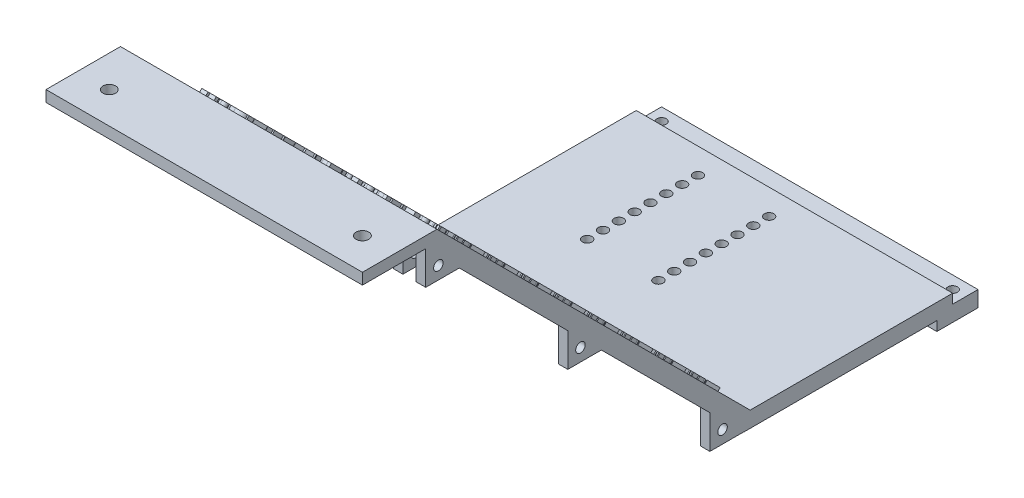
SolidWorks part; units mm, degrees
ref_plane "Front Plane" through (0, 0, 0) normal (0, 0, 1) x (1, 0, 0)
ref_plane "Top Plane" through (0, 0, 0) normal (0, 1, 0) x (1, 0, 0)
ref_plane "Right Plane" through (0, 0, 0) normal (1, 0, 0) x (0, 0, -1)
sketch "Sketch4" plane through (0, 0, 0) normal (1, 0, 0) x (0, 0, -1)
  line L0 (0, 0) -> (-8, 0)
  line L1 (-8, 0) -> (-8, 3)
  line L2 (-8, 3) -> (-72, 3)
  line L3 (-72, 3) -> (-170.9949, 101.9949)
  dimension "D1" = 8
  dimension "D2" = 3
  dimension "D3" = 64
  dimension "D4" = 135
  dimension "D5" = 140
extrude "Extrude-Thin2" add sketch "Sketch4" along normal blind 100 thin thin type one direction reverse wall 5
sketch "Sketch5" plane through (0, 3, 0) normal (0, 1, 0) x (1, 0, 0)
  line L1 (100, -8) -> (100, -72) construction
  line L2 (100, -8) -> (0, -8) construction
  circle A0 centre (50, -16) radius 1.5
  dimension "D2" = 3
  dimension "D1" = 50
  dimension "D3" = 8
extrude "Cut-Extrude1" cut sketch "Sketch5" against normal up to next
pattern_linear "LPattern1" count 8 spacing 5 along (0, 0, 1) count 2 spacing 22.5 along (-1, 0, 0) of "Cut-Extrude1"
sketch "Sketch7" plane through (100, 0, 0) normal (1, 0, 0) x (0, 0, -1)
  line L0 (-170.9949, 101.9949) -> (-174.5305, 101.9949)
  line L1 (-174.5305, 101.9949) -> (-174.5305, 98.4594)
  line L2 (-174.5305, 98.4594) -> (-170.9949, 101.9949)
extrude "Boss-Extrude1" add sketch "Sketch7" against normal up to surface (100 mm away) up to face at (0, 19.2454, 53.3597)
sketch "Sketch8" plane through (0, 0, 174.5305) normal (0, 0, 1) x (1, 0, 0)
  line L1 (0, 101.9949) -> (100, 101.9949)
  line L2 (0, 101.9949) -> (0, 98.4594)
  line L3 (0, 98.4594) -> (100, 98.4594)
  line L4 (100, 101.9949) -> (100, 98.4594)
extrude "Boss-Extrude2" add sketch "Sketch8" along normal blind 20
sketch "Sketch9" plane through (0, 101.9949, 0) normal (0, 1, 0) x (1, 0, 0)
  line L0 (100, -170.9949) -> (100, -194.5305) construction
  line L1 (100, -194.5305) -> (0, -194.5305) construction
  line L2 (0, -170.9949) -> (0, -194.5305) construction
  circle A0 centre (90, -184.5305) radius 2
  circle A1 centre (10, -184.5305) radius 2
  dimension "D1" = 4
  dimension "D2" = 4
  dimension "D3" = 10
  dimension "D4" = 10
  dimension "D5" = 10
  dimension "D6" = 10
extrude "Cut-Extrude2" cut sketch "Sketch9" against normal up to next
sketch "Sketch10" plane through (0, 0, 0) normal (0, 1, 0) x (1, 0, 0)
  line L0 (100, 0) -> (0, 0) construction
  line L1 (100, 0) -> (100, -8) construction
  line L2 (0, 0) -> (0, -8) construction
  circle A0 centre (4, -4) radius 1.5
  circle A1 centre (96, -4) radius 1.5
  dimension "D1" = 3
  dimension "D2" = 3
  dimension "D3" = 4
  dimension "D4" = 4
  dimension "D5" = 4
extrude "Cut-Extrude3" cut sketch "Sketch10" against normal up to next
sketch "Sketch11" plane through (100, 0, 0) normal (1, 0, 0) x (0, 0, -1)
  line L0 (-174.5305, 98.4594) -> (-174.5305, 87.8528)
  line L1 (-174.5305, 87.8528) -> (-163.9239, 87.8528)
  line L2 (-74.0711, -2) -> (-174.5305, 98.4594) construction
  line L3 (-174.5305, 98.4594) -> (-163.9239, 87.8528)
  dimension "D1" = 15
extrude "Boss-Extrude3" add sketch "Sketch11" against normal blind 3
sketch "Sketch12" plane through (100, 0, 0) normal (1, 0, 0) x (0, 0, -1)
  line L0 (-174.5305, 98.4594) -> (-174.5305, 87.8528) construction
  line L1 (-174.5305, 87.8528) -> (-163.9239, 87.8528) construction
  circle A0 centre (-170.5305, 91.8528) radius 1.5
  dimension "D1" = 3
  dimension "D2" = 4
  dimension "D3" = 4
extrude "Cut-Extrude4" cut sketch "Sketch12" against normal up to next
pattern_linear "LPattern2" count 3 spacing 63.5 along (0, -0.7071, -0.7071) count 2 spacing 97 along (-1, 0, 0) of "Boss-Extrude3", "Cut-Extrude4"
sketch "Sketch13" plane through (0, -2, 0) normal (0, -1, 0) x (1, 0, 0)
  line L0 (0, 13) -> (0, 74.0711) construction
  line L1 (0, 48.535) -> (3, 48.535)
  line L2 (0, 48.535) -> (0, 38.535)
  line L3 (0, 38.535) -> (3, 38.535)
  line L4 (3, 48.535) -> (3, 38.535)
  dimension "D1" = 3
  dimension "D2" = 10
  dimension "D3" = 25.535
extrude "Boss-Extrude4" add sketch "Sketch13" along normal blind 10
sketch "Sketch14" plane through (0, 0, 0) normal (-1, 0, 0) x (0, 0, 1)
  line L0 (38.535, -12) -> (38.535, -2) construction
  line L1 (48.535, -12) -> (38.535, -12) construction
  circle A0 centre (43.535, -7) radius 1.5
  dimension "D1" = 3
  dimension "D2" = 5
  dimension "D3" = 5
extrude "Cut-Extrude5" cut sketch "Sketch14" against normal up to next
sketch "Sketch15" plane through (0, -34.5, 34.5) normal (0, 0.7071, -0.7071) x (1, 0, 0)
  line L0 (100, -53.033) -> (100, -193.033) construction
  line L1 (100, -193.033) -> (0, -193.033) construction
  circle A0 centre (84, -176.233) radius 3.4
  circle A1 centre (84, -161.233) radius 3.4
  circle A2 centre (84, -146.233) radius 3.4
  circle A5 centre (84, -131.233) radius 3.4
  circle A6 centre (84, -116.233) radius 3.4
  circle A7 centre (84, -101.233) radius 3.4
  circle A8 centre (84, -86.233) radius 3.4
  circle A9 centre (84, -71.233) radius 3.4
  dimension "D1" = 6.8
  dimension "D2" = 6.8
  dimension "D3" = 6.8
  dimension "D8" = 6.8
  dimension "D9" = 6.8
  dimension "D10" = 6.8
  dimension "D11" = 6.8
  dimension "D16" = 6.8
  dimension "D4" = 16
  dimension "D5" = 16.8
  dimension "D6" = 15
  dimension "D7" = 15
  dimension "D12" = 15
  dimension "D13" = 15
  dimension "D14" = 15
  dimension "D15" = 15
  dimension "D17" = 15
extrude "Cut-Extrude6" cut sketch "Sketch15" against normal up to next
sketch "Sketch16" plane through (0, -34.5, 34.5) normal (0, 0.7071, -0.7071) x (1, 0, 0)
  circle A0 centre (59, -161.233) radius 3.4
  circle A1 centre (44, -161.233) radius 3.4
  circle A2 centre (29, -161.233) radius 3.4
  circle A3 centre (14, -161.233) radius 3.4
  circle A5 centre (84, -161.233) radius 3.4 construction
  circle A6 centre (66.5, -146.233) radius 3.4
  circle A7 centre (51.5, -146.233) radius 3.4
  circle A8 centre (36.5, -146.233) radius 3.4
  circle A9 centre (21.5, -146.233) radius 3.4
  circle A10 centre (6.5, -146.233) radius 3.4
  circle A12 centre (51.5, -131.233) radius 3.4
  circle A13 centre (36.5, -131.233) radius 3.4
  circle A14 centre (21.5, -131.233) radius 3.4
  dimension "D1" = 6.8
  dimension "D2" = 15
  dimension "D3" = 15
  dimension "D7" = 6.8
  dimension "D14" = 6.8
  dimension "D4" = 15
  dimension "D5" = 0
  dimension "D6" = 25
  dimension "D8" = 15
  dimension "D9" = 15
  dimension "D10" = 15
  dimension "D11" = 15
  dimension "D12" = 7.5
  dimension "D13" = 15
  dimension "D15" = 15
  dimension "D16" = 15
  dimension "D17" = 15
extrude "Cut-Extrude7" cut sketch "Sketch16" against normal up to next
sketch "Sketch17" plane through (0, -34.5, 34.5) normal (0, 0.7071, -0.7071) x (1, 0, 0)
  circle A0 centre (51.5, -111.233) radius 3.4
  circle A1 centre (36.5, -106.233) radius 3.4
  circle A2 centre (21.5, -111.233) radius 3.4
  circle A3 centre (36.5, -131.233) radius 3.4 construction
  circle A4 centre (84, -116.233) radius 3.4 construction
  dimension "D1" = 6.8
  dimension "D4" = 5
  dimension "D2" = 15
  dimension "D3" = 15
  dimension "D5" = 0
  dimension "D6" = 5
extrude "Cut-Extrude8" cut sketch "Sketch17" against normal up to next
pattern_linear "LPattern3" count 4 spacing 15 along (0, -0.7071, -0.7071) of "Cut-Extrude8"
ref_plane "Plane1" through (0, -34.5, 34.5) normal (0, 0.7071, -0.7071) x (-1, 0, 0)
sketch "Sketch19" plane through (0, -34.5, 34.5) normal (0, 0.7071, -0.7071) x (-1, 0, 0)
  circle A0 centre (-84, 176.233) radius 3.4 construction
  text T0 "SENDS" font "Century Gothic" height 5
  dimension "D1" = 10
  dimension "D2" = 8
extrude "Boss-Extrude5" add sketch "Sketch19" along normal blind 1
sketch "Sketch21" plane through (0, -34.5, 34.5) normal (0, 0.7071, -0.7071) x (-1, 0, 0)
  circle A0 centre (-59, 161.233) radius 3.4 construction
  circle A1 centre (-44, 161.233) radius 3.4 construction
  circle A2 centre (-29, 161.233) radius 3.4 construction
  circle A3 centre (-14, 161.233) radius 3.4 construction
  circle A4 centre (-36.5, 146.233) radius 3.4 construction
  circle A5 centre (-66.5, 146.233) radius 3.4 construction
  circle A6 centre (-51.5, 146.233) radius 3.4 construction
  circle A7 centre (-21.5, 146.233) radius 3.4 construction
  circle A8 centre (-6.5, 146.233) radius 3.4 construction
  circle A9 centre (-51.5, 131.233) radius 3.4 construction
  circle A10 centre (-36.5, 131.233) radius 3.4 construction
  circle A11 centre (-21.5, 131.233) radius 3.4 construction
  text T0 "DYANMICS\r\n" font "Century Gothic" height 5
  text T1 "THRESH"
  text T2 "ATK"
  text T3 "RLS"
  text T4 "KNEE"
  text T5 "THRESH"
  text T6 "ATK"
  text T7 "RLS"
  text T8 "KNEE"
  text T9 "RATIO" font "Century Gothic" height 3
  text T10 "THRESH"
  text T11 "ATK"
  text T12 "RLS"
  dimension "D1" = 8
  dimension "D2" = 4.25
  dimension "D3" = 4
  dimension "D4" = 6
  dimension "D5" = 20
  dimension "D6" = 8
  dimension "D7" = 5
  dimension "D8" = 5
  dimension "D9" = 4.25
  dimension "D10" = 4
  dimension "D11" = 6
  dimension "D12" = 6
  dimension "D13" = 12.5
  dimension "D14" = 8
  dimension "D15" = 5
  dimension "D16" = 4.25
  dimension "D17" = 4
extrude "Boss-Extrude6" add sketch "Sketch21" along normal blind 1
sketch "Sketch23" plane through (0, -34.5, 34.5) normal (0, 0.7071, -0.7071) x (-1, 0, 0)
  circle A0 centre (-51.5, 111.233) radius 3.4 construction
  circle A1 centre (-36.5, 106.233) radius 3.4 construction
  circle A2 centre (-21.5, 111.233) radius 3.4 construction
  text T0 "Q" font "Century Gothic" height 5
  text T1 "F" font "Century Gothic" height 5
  text T2 "G" font "Century Gothic" height 5
  text T3 "EQ" font "Century Gothic" height 5
  dimension "D1" = 2.7
  dimension "D2" = 6.5
  dimension "D3" = 6.5
  dimension "D4" = 2
  dimension "D5" = 2.7
  dimension "D6" = 4
  dimension "D7" = 7
extrude "Boss-Extrude7" add sketch "Sketch23" along normal blind 1
sketch "Sketch24" plane through (0, -34.5, 34.5) normal (0, 0.7071, -0.7071) x (-1, 0, 0)
  circle A0 centre (-84, 176.233) radius 3.4 construction
  circle A1 centre (-84, 161.233) radius 3.4 construction
  circle A2 centre (-84, 146.233) radius 3.4 construction
  circle A3 centre (-84, 131.233) radius 3.4 construction
  circle A4 centre (-84, 116.233) radius 3.4 construction
  circle A5 centre (-84, 101.233) radius 3.4 construction
  circle A6 centre (-84, 86.233) radius 3.4 construction
  circle A7 centre (-84, 71.233) radius 3.4 construction
  text T0 "AUX 1"
  text T1 "AUX 2"
  text T2 "AUX 3"
  text T3 "AUX 4"
  text T4 "AUX 5"
  text T5 "AUX 6"
  text T6 "AUX 7"
  text T7 "AUX 8"
  dimension "D1" = 9
  dimension "D2" = 12.5
  dimension "D3" = 9
  dimension "D4" = 9
  dimension "D5" = 9
  dimension "D6" = 9
  dimension "D7" = 9
  dimension "D8" = 9
  dimension "D9" = 9
extrude "Boss-Extrude8" add sketch "Sketch24" along normal blind 1
